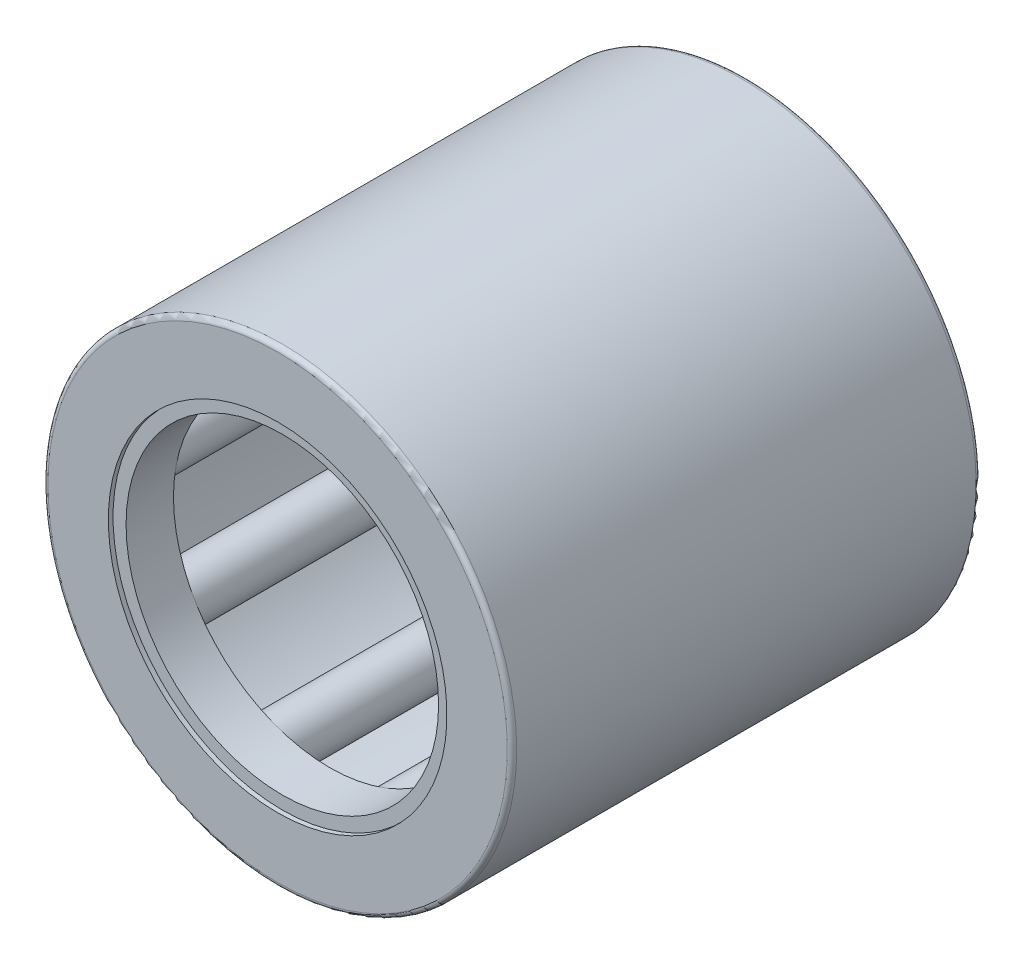
SolidWorks part; units mm, degrees
material "Alloy Steel"
ref_plane "Front Plane" through (0, 0, 0) normal (0, 0, 1) x (1, 0, 0)
ref_plane "Top Plane" through (0, 0, 0) normal (0, 1, 0) x (1, 0, 0)
ref_plane "Right Plane" through (0, 0, 0) normal (1, 0, 0) x (0, 0, -1)
sketch "Sketch1" plane through (0, 0, 0) normal (1, 0, 0) x (0, 0, -1)
  line L0 (-6, 0) -> (6, 0) construction
  line L1 (0, 0) -> (0, 6) construction
  line L2 (-6, 0) -> (-6, 6) construction
  line L3 (-6, 6) -> (6, 6)
  line L4 (6, 6) -> (6, 0) construction
  line L5 (6, 0) -> (5.3333, 0) construction
  line L6 (5.3333, 0) -> (5.3333, 5.3333) construction
  line L7 (5.3333, 5.3333) -> (-5.3333, 5.3333)
  line L8 (-5.3333, 5.3333) -> (-5.3333, 0) construction
  line L9 (-5.3333, 0) -> (-6, 0) construction
  line L10 (-6, 6) -> (-6, 4.3333)
  line L11 (-6, 4.3333) -> (-5.3333, 4.3333)
  line L12 (-5.3333, 4.3333) -> (-5.3333, 5.3333)
  line L13 (5.3333, 6) -> (5.3333, 5.3333) construction
  line L14 (5.3333, 5.3333) -> (5.3333, 4.3333)
  line L15 (5.3333, 4.3333) -> (6, 4.3333)
  line L16 (6, 4.3333) -> (6, 6)
  line L17 (5.3333, 5.3333) -> (5.3333, 4.6667) construction
  line L18 (5.3333, 4.6667) -> (5.3333, 4) construction
  line L19 (5.3333, -5.3333) -> (5.3333, -4.6667) construction
  line L20 (5.3333, -6) -> (5.3333, -5.3333) construction
  line L21 (6, -4.3333) -> (6, -6) construction
  line L22 (5.3333, -4.3333) -> (6, -4.3333) construction
  line L23 (5.3333, -5.3333) -> (5.3333, -4.3333) construction
  line L24 (-5.3333, -4.3333) -> (-5.3333, -5.3333) construction
  line L25 (-6, -4.3333) -> (-5.3333, -4.3333) construction
  line L26 (-6, -6) -> (-6, -4.3333) construction
  line L27 (5.3333, -5.3333) -> (-5.3333, -5.3333) construction
  line L28 (-6, -6) -> (6, -6) construction
  point P4 (0, 4)
  dimension "C | Width" = 12
  dimension "Fw | ID" = 8
  dimension "D | OD" = 12
sketch "Sketch7" plane through (0, 0, 0) normal (1, 0, 0) x (0, 0, -1)
  line L0 (-6, 6) -> (-6, 4.3333) construction
  line L1 (-6, 4.3333) -> (-5.3333, 4.3333) construction
  line L2 (-5.3333, 4.3333) -> (-5.3333, 5.3333) construction
  line L3 (5.3333, 5.3333) -> (-5.3333, 5.3333) construction
  line L4 (5.3333, 5.3333) -> (5.3333, 4.3333) construction
  line L5 (5.3333, 4.3333) -> (6, 4.3333) construction
  line L6 (6, 4.3333) -> (6, 6) construction
  line L8 (-6, 6) -> (6, 6) construction
  line L9 (-6, 6) -> (-6, 4.3333)
  line L10 (-6, 4.3333) -> (-5.3333, 4.3333)
  line L13 (-5.3333, 4.3333) -> (-5.3333, 5.3333)
  line L16 (5.3333, 5.3333) -> (-5.3333, 5.3333)
  line L17 (5.3333, 5.3333) -> (5.3333, 4.3333)
  line L18 (5.3333, 4.3333) -> (6, 4.3333)
  line L19 (6, 4.3333) -> (6, 6)
  line L20 (-6, 6) -> (6, 6)
revolve "Revolve1" add sketch "Sketch7" angle 360 about L0
sketch "Sketch2" plane through (0, 0, 0) normal (1, 0, 0) x (0, 0, -1)
  line L0 (-6, 4.3333) -> (-5.3333, 4.3333) construction
  line L1 (-4.6667, 4.6667) -> (4.6667, 4.6667) construction
  line L2 (-4.6667, 4.6667) -> (-4.6667, 5.3333) construction
  line L3 (-4.6667, 5.3333) -> (4.6667, 5.3333)
  line L4 (4.6667, 4.6667) -> (4.6667, 5.3333) construction
  line L5 (5.3333, 4.3333) -> (6, 4.3333) construction
  line L6 (-5.3333, 4.6667) -> (-4.6667, 4.6667) construction
  line L7 (4.6667, 4.6667) -> (5.3333, 4.6667) construction
  line L8 (6, 6) -> (6, 0) construction
  line L9 (-4.6667, 4.8333) -> (-4.6667, 4.5) construction
  line L10 (-5.3333, 4.6667) -> (-5.3333, 4.3333) construction
  line L11 (-4.6667, 5.3333) -> (-4.6667, 4.8333)
  line L12 (4.6667, 5.3333) -> (4.6667, 4.8333)
  line L13 (4.6667, 4.8333) -> (-4.6667, 4.8333)
  line L14 (0, 5.3333) -> (0, 4) construction
  line L16 (-4.6667, 4.5) -> (-5.3333, 4.5) construction
  line L17 (0, 0) -> (6, 0) construction
  line L18 (-4.6667, -4.5) -> (-5.3333, -4.5) construction
  line L19 (0, -5.3333) -> (0, -4) construction
  line L20 (-5.3333, -4.6667) -> (-5.3333, -4.3333) construction
  line L21 (-4.6667, -4.8333) -> (-4.6667, -4.5) construction
  line L22 (4.6667, -4.6667) -> (5.3333, -4.6667) construction
  line L23 (-5.3333, -4.6667) -> (-4.6667, -4.6667) construction
  line L24 (4.6667, -4.6667) -> (4.6667, -5.3333) construction
  line L25 (-4.6667, -4.6667) -> (-4.6667, -5.3333) construction
  line L26 (-4.6667, -4.6667) -> (4.6667, -4.6667) construction
  line L27 (4.6667, -4.8333) -> (-4.6667, -4.8333) construction
  line L28 (4.6667, -5.3333) -> (4.6667, -4.8333) construction
  line L29 (-4.6667, -5.3333) -> (-4.6667, -4.8333) construction
  line L30 (-4.6667, -5.3333) -> (4.6667, -5.3333) construction
  line L33 (5.3333, 5.3333) -> (-5.3333, 5.3333) construction
  line L34 (5.3333, 5.3333) -> (5.3333, 4.3333) construction
  line L35 (-5.3333, 4.3333) -> (-5.3333, 5.3333) construction
  line L36 (0, 0) -> (0, 6) construction
  point P16 (0, 4.6667)
revolve "Revolve2" add sketch "Sketch2" angle 360 about L1
sketch "Sketch3" plane through (0, 0, 0) normal (1, 0, 0) x (0, 0, -1)
  line L1 (-5.3333, 4.6667) -> (5.3333, 4.6667)
  line L2 (-5.3333, 4.6667) -> (-5.3333, 4.8333)
  line L3 (-5.3333, 4.8333) -> (5.3333, 4.8333)
  line L4 (5.3333, 4.6667) -> (5.3333, 4.8333)
  line L5 (0, 0) -> (6, 0) construction
  line L7 (5.3333, -4.6667) -> (5.3333, -4.8333) construction
  line L8 (-5.3333, -4.8333) -> (5.3333, -4.8333) construction
  line L9 (-5.3333, -4.6667) -> (-5.3333, -4.8333) construction
  line L10 (-5.3333, -4.6667) -> (5.3333, -4.6667) construction
  line L11 (5.3333, 5.3333) -> (5.3333, 4.3333) construction
  line L12 (6, 6) -> (6, 0) construction
revolve "Revolve3" add sketch "Sketch3" angle 360 about L1
ref_axis "Axis1" through (0, 4.3333, 6) along (0, 1, 0)
pattern_circular "CirPattern1" count 9 every 40 about axis through (0, 0, 6) along (0, 0, -1) of bodies 166 167
fillet "Fillet1" radius 0.12 2 edges at (0, -6, -6) (0, -6, 6)
sketch "Sketch4" plane through (0, 0, 0) normal (1, 0, 0) x (0, 0, -1)
  line L0 (4.6667, 5.3333) -> (4.6667, 4.8333) construction
  line L1 (5.88, 4) -> (4.6667, 4)
  line L2 (5.88, 4) -> (5.88, 4.3333)
  line L3 (5.88, 4.3333) -> (4.6667, 4.3333)
  line L4 (4.6667, 4) -> (4.6667, 4.3333)
  line L7 (5.3333, 4.3333) -> (6, 4.3333) construction
  line L8 (5.88, -6) -> (5.88, 6) construction
revolve "Revolve4" add sketch "Sketch4" angle 360 about L0
sketch "Sketch5" plane through (0, 0, 0) normal (1, 0, 0) x (0, 0, -1)
  line L0 (-5.88, 6) -> (-5.88, -6) construction
  line L1 (-4.6667, 4) -> (-5.88, 4)
  line L2 (-4.6667, 4) -> (-4.6667, 4.3333)
  line L3 (-4.6667, 4.3333) -> (-5.88, 4.3333)
  line L4 (-5.88, 4) -> (-5.88, 4.3333)
  line L5 (-4.6667, 5.3333) -> (-4.6667, 4.8333) construction
  line L6 (-6, 4.3333) -> (-5.3333, 4.3333) construction
revolve "Revolve5" add sketch "Sketch5" angle 360 about L0
sketch "Front View" plane through (0, 0, 0) normal (0, 0, 1) x (1, 0, 0)
  circle A0 centre (0, 0) radius 4 construction
  circle A1 centre (0, 0) radius 6 construction
  dimension "ID" = 8
  dimension "OD" = 12
sketch "Right View" plane through (0, 0, 0) normal (1, 0, 0) x (0, 0, -1)
  line L0 (-6, 6) -> (6, 6) construction
  line L1 (-6, 6) -> (6, 6) construction
  line L2 (0, 0) -> (0, 6) construction
  point P4 (0, 6)
  dimension "Width" = 12
ref_axis "Axis2" through (0, 0, -5.88) along (0, 0, 1)
equation "\"Rollers@CirPattern1\"  = \"OD@Sketch1\"*.75"
equation "\"D1@Fillet1\" = \"D | OD@Sketch1\" * .01"
equation "\"Angle@CirPattern1\"=360 / \"Rollers@CirPattern1\""
equation "\"ID@Front View\" = \"Fw | ID@Sketch1\""
equation "\"OD@Front View\" = \"D | OD@Sketch1\""
equation "\"Width@Right View\" = \"C | Width@Sketch1\""
